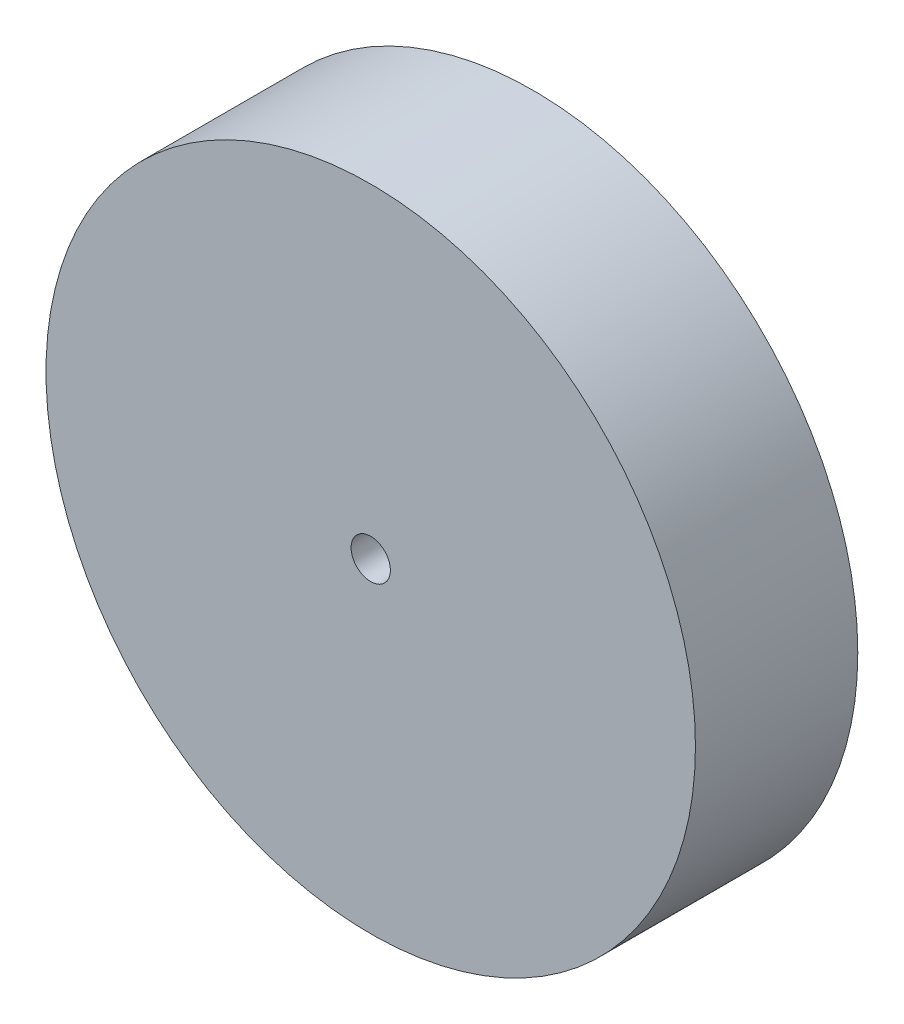
SolidWorks part; units mm, degrees
material "POLIURETANICHE (11671)"
ref_plane "Piano frontale" through (0, 0, 0) normal (0, 0, 1) x (1, 0, 0)
ref_plane "Piano superiore" through (0, 0, 0) normal (0, 1, 0) x (1, 0, 0)
ref_plane "Piano destro" through (0, 0, 0) normal (1, 0, 0) x (0, 0, -1)
sketch "Schizzo1" plane through (0, 0, 0) normal (0, 0, 1) x (1, 0, 0)
  circle A0 centre (0, 0) radius 100
  circle A1 centre (0, 0) radius 6.05
  dimension "D1" = 200
  dimension "D2" = 12.1
extrude "Estrusione-Estrusione1" add sketch "Schizzo1" along normal mid plane 50
sketch3d "Schizzo3D1"
  point P0 (0, 0, 0)
ref_axis "Assi1" through (0, 0, 62.6228) along (0, 0, -1)
ref_point "Punto1"
